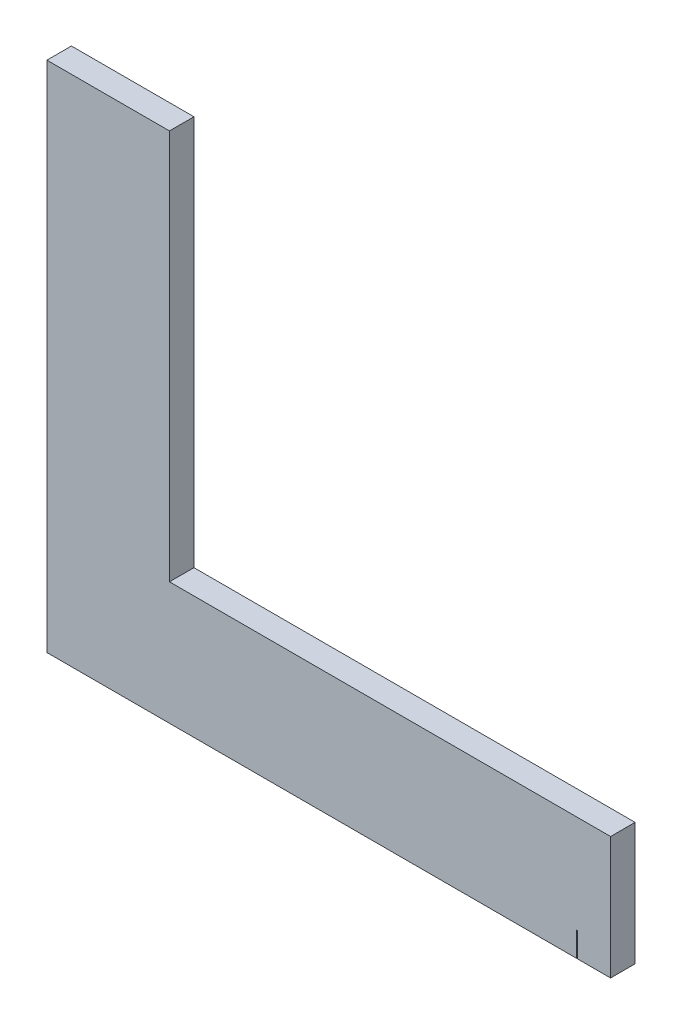
SolidWorks part; units mm, degrees
ref_plane "Front Plane" through (0, 0, 0) normal (0, 0, 1) x (1, 0, 0)
ref_plane "Top Plane" through (0, 0, 0) normal (0, 1, 0) x (1, 0, 0)
ref_plane "Right Plane" through (0, 0, 0) normal (1, 0, 0) x (0, 0, -1)
sketch "Sketch1" plane through (0, 0, 0) normal (0, 0, 1) x (1, 0, 0)
  line L0 (0, 0) -> (0, -62.8)
  line L1 (0, -62.8) -> (69, -62.8)
  line L2 (69, -62.8) -> (69, -47.8)
  line L3 (69, -47.8) -> (15, -47.8)
  line L4 (15, -47.8) -> (15, 0)
  line L5 (15, 0) -> (0, 0)
  dimension "D1" = 47.8
  dimension "D2" = 15
  dimension "D3" = 69
  dimension "D4" = 15
extrude "Boss-Extrude1" add sketch "Sketch1" along normal blind 3
sketch "Sketch2" plane through (0, -62.8, 0) normal (0, -1, 0) x (1, 0, 0)
  line L0 (0, 1.5) -> (64.9, 1.5) construction
  line L1 (0, 3) -> (0, 0) construction
  line L2 (0, 3) -> (69, 3) construction
  line L3 (64.85, 0) -> (64.95, 0)
  line L4 (64.85, 0) -> (64.85, 3)
  line L5 (64.85, 3) -> (64.95, 3)
  line L6 (64.95, 0) -> (64.95, 3)
  line L7 (64.85, 0) -> (64.95, 3) construction
  line L8 (64.85, 3) -> (64.95, 0) construction
  dimension "D1" = 64.9
extrude "Cut-Extrude2" cut sketch "Sketch2" against normal blind 3
equation "\"A.L\"= 0.06m"
equation "\"A.h\"= 0.005m"
equation "\"A.d\"= 0.003m"
equation "\"A.delta\"= 45.0001"
equation "\"A.w\"= 0.02m"
equation "\"A.v\"= 0.03m"
equation "\"A.s\"= 0.0075m"
equation "\"A.t\"= 0.005m"
equation "\"B.L\"= 0.04m"
equation "\"B.h\"= 0.004m"
equation "\"B.s\"= 0.008m"
equation "\"B.t\"= 0.004m"
equation "\"C.h\"= 0.0062m"
equation "\"C.d\"= 0.003m"
equation "\"C.L\"= 0.05m"
equation "\"C.wmax\"= 0.005m"
equation "\"D.L\"= 0.045m"
equation "\"D.h\"= 0.004m"
equation "\"D.s\"= 0.01m"
equation "\"D.t\"= 0.004m"
equation "\"a_h\"= 0.0001m"
equation "\"a_d\"= 0.003m"
equation "\"a_L\"= 0.01m"
equation "\"b_h\"= 0.0004m"
equation "\"b_d\"= 0.003m"
equation "\"b_L\"= 0.01m"
equation "\"c_h\"= 0.0001m"
equation "\"c_d\"= 0.003m"
equation "\"c_L\"= 0.01m"
equation "\"d_h\"= 0.0001m"
equation "\"d_d\"= 0.003m"
equation "\"d_L\"= 0.01m"
equation "\"S.h\"= 0.015m"
equation "\"S.L\"= 0.0559m"
equation "\"D1@Sketch1\"=\"S.L\"-\"C.wmax\"-\"C.h\"/2"
equation "\"D2@Sketch1\"=\"S.h\""
equation "\"D3@Sketch1\"=\"C.L\"+\"S.h\"+0.004"
equation "\"D4@Sketch1\"=\"S.h\""
equation "\"D1@Boss-Extrude1\"=\"A.d\""
equation "\"D1@Sketch2\"=\"C.L\"+\"S.h\"-\"d_h\""
equation "\"D2@Sketch2\"=\"d_h\""
